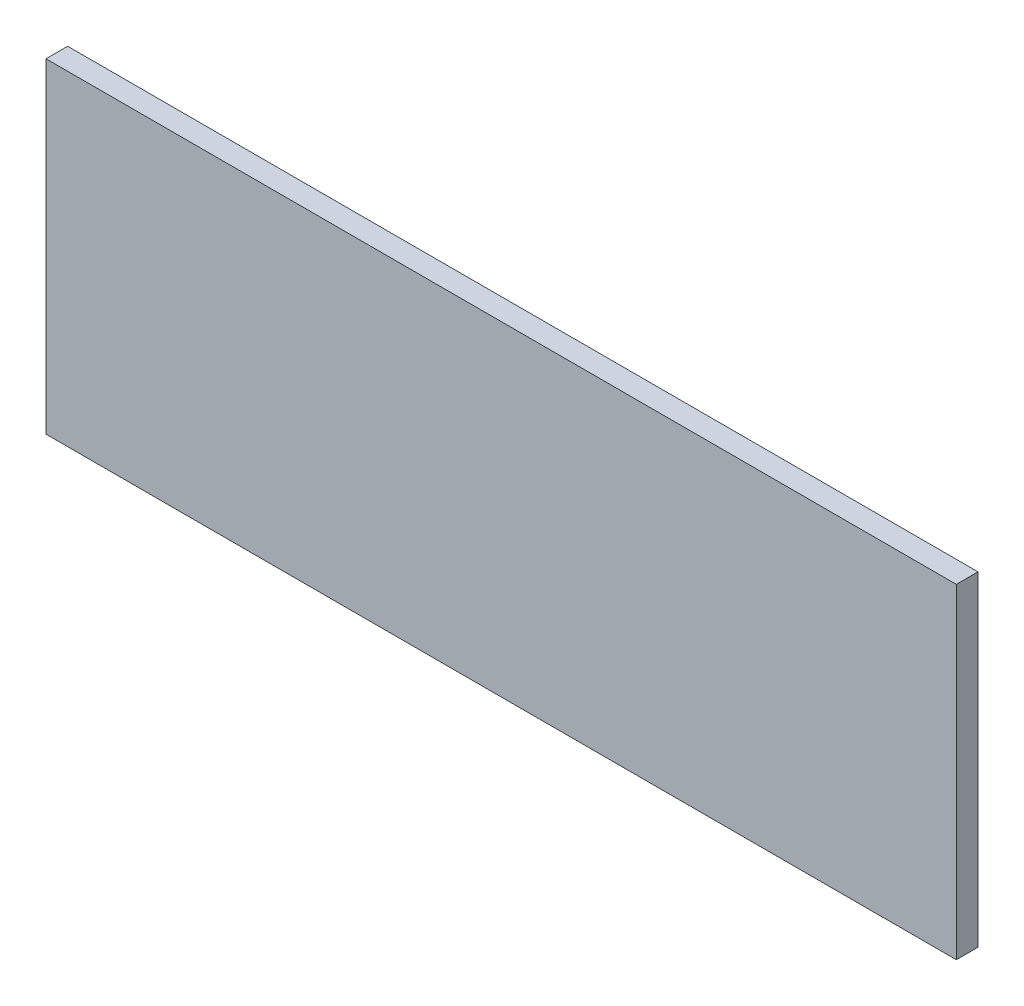
SolidWorks part; units mm, degrees
ref_plane "正面" through (0, 0, 0) normal (0, 0, 1) x (1, 0, 0)
ref_plane "平面" through (0, 0, 0) normal (0, 1, 0) x (1, 0, 0)
ref_plane "右側面" through (0, 0, 0) normal (1, 0, 0) x (0, 0, -1)
sketch "ｽｹｯﾁ1" plane through (0, 0, 0) normal (0, 0, 1) x (1, 0, 0)
  line L1 (-69.2801, 161.5071) -> (350.7199, 161.5071)
  line L2 (-69.2801, 161.5071) -> (-69.2801, 11.5071)
  line L3 (-69.2801, 11.5071) -> (350.7199, 11.5071)
  line L4 (350.7199, 161.5071) -> (350.7199, 11.5071)
  dimension "D1" = 420
  dimension "D3" = 150
extrude "ﾎﾞｽ - 押し出し1" add sketch "ｽｹｯﾁ1" along normal blind 10
